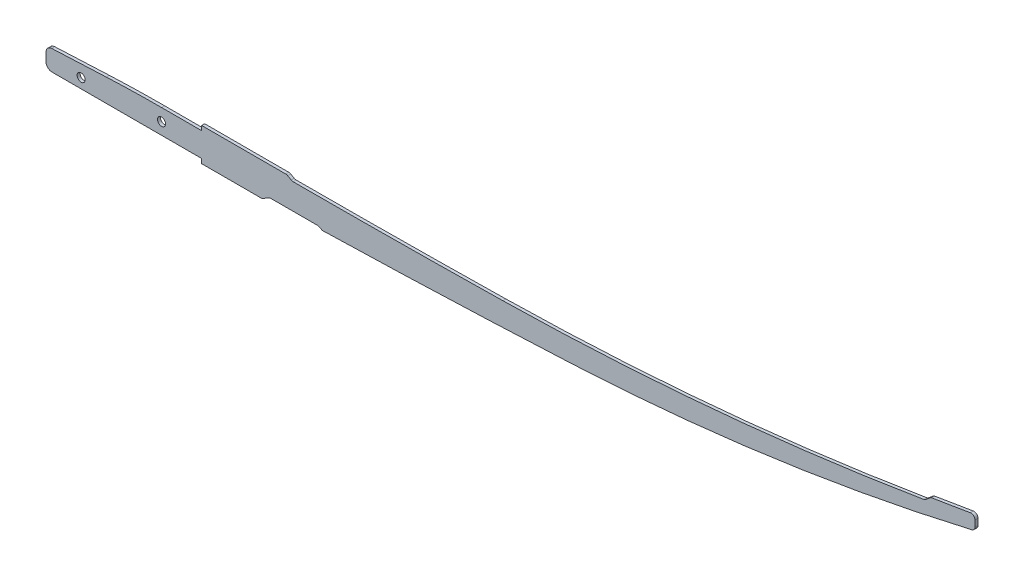
SolidWorks part; units mm, degrees
ref_plane "前视基准面" through (0, 0, 0) normal (0, 0, 1) x (1, 0, 0)
ref_plane "上视基准面" through (0, 0, 0) normal (0, 1, 0) x (1, 0, 0)
ref_plane "右视基准面" through (0, 0, 0) normal (1, 0, 0) x (0, 0, -1)
sketch "草图1" plane through (0, 0, 0) normal (0, 0, 1) x (1, 0, 0)
  line L0 (0, 81.9069) -> (0, 12) construction
  line L1 (0, 16.5) -> (84.8038, 16.5)
  line L2 (84.8038, 16.5) -> (90, 13.5)
  line L3 (0, -16.5) -> (60, -16.5)
  line L4 (60, -16.5) -> (67.7942, -12)
  line L5 (67.7942, -12) -> (116.5359, -12)
  line L6 (116.5359, -12) -> (120, -14)
  line L7 (0, 16.5) -> (0, 12)
  line L8 (-48.3677, 0) -> (26.6044, 0) construction
  line L9 (720, 53.6929) -> (726.0954, 58.7056)
  line L10 (726.0954, 58.7056) -> (770, 66)
  line L11 (770, 66) -> (770, 52)
  line L12 (90, 13.5) -> (0, 13.5) construction
  line L13 (720, 53.6929) -> (770, 62) construction
  line L14 (120, -14) -> (0, -14) construction
  line L15 (120, -14) -> (0, -17) construction
  line L16 (0, 12) -> (-40, 12)
  line L17 (0, -12) -> (-149, -12)
  line L21 (0, -12) -> (0, -16.5)
  line L22 (0, 12) -> (0, 0) construction
  line L23 (0, -12) -> (0, -75.7106) construction
  line L24 (-95, 10.7433) -> (-149.274, 8.2618)
  line L26 (-155, 2.2681) -> (-155, -6)
  arc A0 (90, 13.5) -> (300, 15.3376) centre (90, 12013.5) ccw
  arc A1 (120, -14) -> (370, -4.6196) centre (-129.9219, 9982.8765) ccw
  arc A2 (300, 15.3376) -> (720, 53.6929) centre (249.7935, 2883.8437) ccw
  arc A3 (370, -4.6196) -> (770, 52) centre (258.3915, 2225.107) ccw
  arc A4 (-4, 0) -> (-160, -4) centre (-4, -3044) ccw construction
  circle A8 centre (-40.0007, -0.2129) radius 4.01
  circle A9 centre (-120, -2.2111) radius 4.01
  arc A10 (-149, -12) -> (-155, -6) centre (-149, -6) cw
  arc A11 (-40, 12) -> (-95, 10.7433) centre (-40, -1192.1843) ccw
  arc A12 (-149.274, 8.2618) -> (-155, 2.2681) centre (-149, 2.2681) ccw
  point P40 (-155, 8)
  dimension "D1" = 770
  dimension "D3" = 300
  dimension "D16" = 52
  dimension "D17" = 50
  dimension "D19" = 12000
  dimension "D20" = 10000
  dimension "D22" = 4
  dimension "D24" = 4
  dimension "D29" = 60
  dimension "D30" = 8.02
  dimension "D32" = 8.02
  dimension "D23" = 40
  dimension "D33" = 6
  dimension "D2" = 33
  dimension "D4" = 400
  dimension "D5" = 30
  dimension "D6" = 30
  dimension "D7" = 30
  dimension "D8" = 30
  dimension "D9" = 14
  dimension "D10" = 120
  dimension "D11" = 90
  dimension "D12" = 3
  dimension "D13" = 5
  dimension "D14" = 2
  dimension "D15" = 60
  dimension "D18" = 10
  dimension "D21" = 3
  dimension "D25" = 155
  dimension "D26" = 4
  dimension "D27" = 160
  dimension "D28" = 24
  dimension "D31" = 40
  dimension "D34" = 40.0007
extrude "凸台-拉伸1" add sketch "草图1" along normal mid plane 3 contours L16 L17 L7 | A1 A3 L11 L10 L9 A2 A0 L2 L1 L7 L3 L4 L5 L6 region at (265.9618, 9.3823, 0)
fillet "圆角1" radius 4 2 edges at (770, 66, 0) (770, 52, 0)
fillet "圆角3" radius 4 8 edges at (720, 53.6929, 0) (726.0954, 58.7056, 0) (90, 13.5, 0) (84.8038, 16.5, 0) (120, -14, 0) (116.5359, -12, 0) (67.7942, -12, 0) (60, -16.5, 0)
